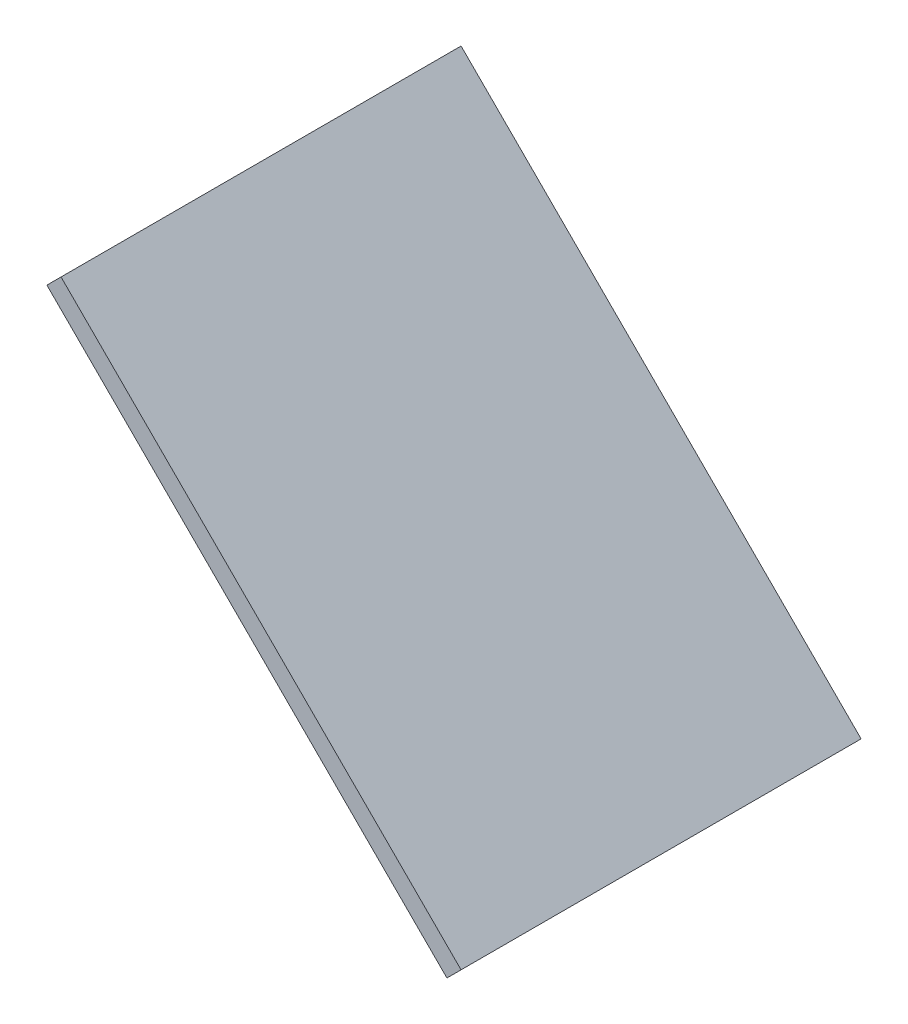
SolidWorks part; units mm, degrees
ref_plane "Front Plane" through (0, 0, 0) normal (0, 0, 1) x (1, 0, 0)
ref_plane "Top Plane" through (0, 0, 0) normal (0, 1, 0) x (1, 0, 0)
ref_plane "Right Plane" through (0, 0, 0) normal (1, 0, 0) x (0, 0, -1)
sketch "Sketch1" plane through (0, 0, 0) normal (0, 0, 1) x (1, 0, 0)
  line L0 (-127, 0) -> (0, -127)
  line L1 (-127, 0) -> (-122.5099, 4.4901)
  line L2 (0, -127) -> (4.4901, -122.5099)
  line L3 (-122.5099, 4.4901) -> (4.4901, -122.5099)
  dimension "D1" = 6.35
extrude "Boss-Extrude1" add sketch "Sketch1" along normal blind 127
